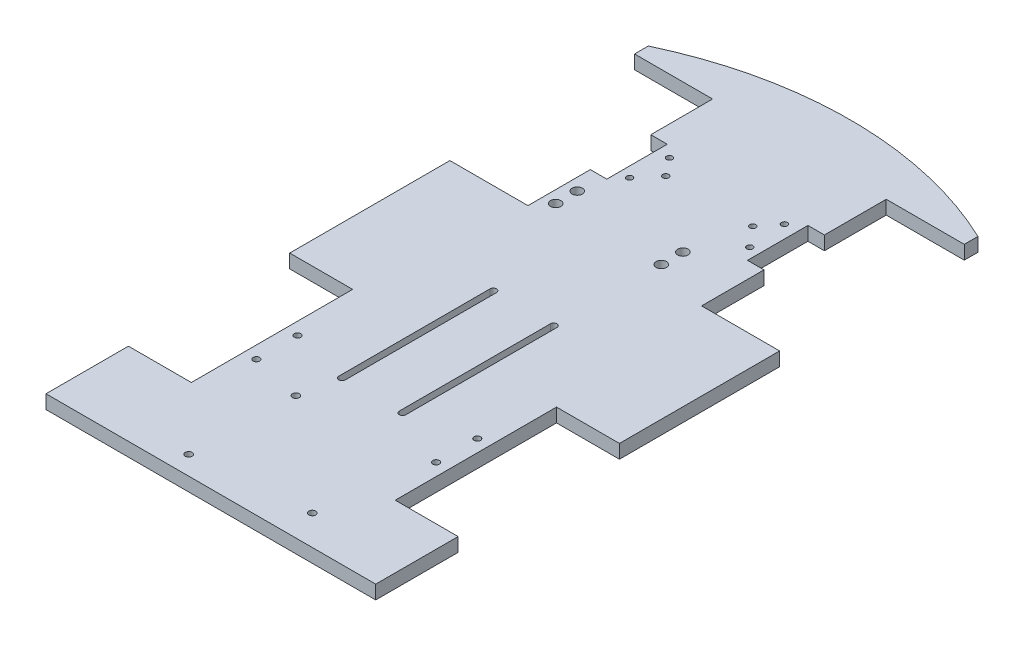
SolidWorks part; units mm, degrees
material "Oak"
ref_plane "Front Plane" through (0, 0, 0) normal (0, 0, 1) x (1, 0, 0)
ref_plane "Top Plane" through (0, 0, 0) normal (0, 1, 0) x (1, 0, 0)
ref_plane "Right Plane" through (0, 0, 0) normal (1, 0, 0) x (0, 0, -1)
sketch "Sketch1" plane through (0, 0, 0) normal (0, 1, 0) x (1, 0, 0)
  line L0 (50.292, 32.512) -> (76.2, 32.512) construction
  line L1 (0, 0) -> (0, -280.955) construction
  line L2 (0, 66.1738) -> (0, -229.362)
  line L3 (76.2, -229.362) -> (0, -229.362)
  line L7 (50.292, 32.512) -> (50.292, -32.512) construction
  line L8 (50.292, -32.512) -> (76.2, -32.512) construction
  line L9 (76.2, 32.512) -> (76.2, -32.512) construction
  line L10 (50.292, 32.512) -> (76.2, -32.512) construction
  line L11 (50.292, -32.512) -> (76.2, 32.512) construction
  line L18 (50.292, -119.888) -> (76.2, -119.888) construction
  line L19 (50.292, -119.888) -> (50.292, -184.912) construction
  line L20 (50.292, -184.912) -> (76.2, -184.912) construction
  line L21 (76.2, -119.888) -> (76.2, -184.912) construction
  line L22 (50.292, -119.888) -> (76.2, -184.912) construction
  line L23 (50.292, -184.912) -> (76.2, -119.888) construction
  line L25 (-76.2, 0) -> (76.2, 0) construction
  line L27 (-76.2, -152.4) -> (76.2, -152.4) construction
  line L28 (76.2, 0) -> (76.2, -152.4) construction
  line L33 (40.132, -42.672) -> (76.2, -42.672)
  line L34 (40.132, 42.672) -> (40.132, 14.097)
  line L35 (40.132, 42.672) -> (76.2, 42.672)
  line L36 (47.117, -191.262) -> (76.2, -191.262)
  line L37 (47.117, -116.713) -> (47.117, -191.262)
  line L38 (47.117, -116.713) -> (76.2, -116.713)
  line L43 (76.2, -42.672) -> (76.2, -116.713)
  line L45 (76.2, 42.672) -> (76.2, 49.022)
  line L47 (76.2, -191.262) -> (76.2, -229.362)
  line L55 (32.512, -13.843) -> (40.132, -13.843)
  line L56 (32.512, 14.097) -> (32.512, -13.843)
  line L57 (32.512, 14.097) -> (40.132, 14.097)
  line L58 (40.132, -13.843) -> (40.132, -42.672)
  arc A0 (0, 66.1738) -> (76.2, 49.022) centre (0, -111.6688) cw
  point P9 (63.246, 0)
  point P19 (63.246, -152.4)
  dimension "D7" = 3.175
  dimension "D8" = 6.35
  dimension "D12" = 7.62
  dimension "D16" = 6.35
  dimension "D1" = 152.4
  dimension "D2" = 152.4
  dimension "D3" = 126.492
  dimension "D4" = 25.908
  dimension "D6" = 3.175
  dimension "D9" = 10.16
  dimension "D10" = 10.16
  dimension "D5" = 65.024
  dimension "D11" = 10.16
  dimension "D13" = 27.94
  dimension "D14" = 28.575
  dimension "D15" = 38.1
extrude "Chassis" add sketch "Sketch1" along normal blind 6.35 contours L47 L36 L37 L38 L43 L33 L34 L55 L56 L57 L35 L45 region at (30.845, 0, 91.965)
mirror "Mirror1" about plane through (0, 6.35, 0) normal (1, 0, 0) of "Chassis"
sketch "Sketch2" plane through (0, 0, 0) normal (0, 1, 0) x (1, 0, 0)
  line L0 (-47.117, -116.713) -> (-47.117, -191.262) construction
  line L1 (-47.117, -191.262) -> (-76.2, -191.262) construction
  line L2 (47.117, -116.713) -> (47.117, -191.262) construction
  line L3 (47.117, -191.262) -> (76.2, -191.262) construction
  line L4 (15.367, -84.7659) -> (15.367, -154.6159)
  line L5 (12.367, -84.7659) -> (12.367, -154.6159)
  line L6 (-12.573, -84.7659) -> (-12.573, -154.6159)
  line L7 (-15.573, -84.7659) -> (-15.573, -154.6159)
  line L8 (47.117, -116.713) -> (76.2, -116.713) construction
  circle A0 centre (-26.5557, 9.17) radius 1.3716 construction
  circle A1 centre (-17.7031, -172.3599) radius 1.5875
  circle A2 centre (-17.7031, -172.3599) radius 1.5875
  circle A3 centre (-18.9731, -220.6199) radius 1.5875
  circle A4 centre (-18.9731, -220.6199) radius 1.5875
  circle A5 centre (33.0969, -215.5399) radius 1.5875
  circle A6 centre (33.0969, -215.5399) radius 1.5875
  circle A7 centre (-20.1056, 0.9994) radius 1.3716 construction
  circle A8 centre (-27.7865, -8.0406) radius 1.3716 construction
  circle A9 centre (26.5557, 9.17) radius 1.3716 construction
  circle A10 centre (20.1056, 0.9994) radius 1.3716 construction
  circle A11 centre (27.7865, -8.0406) radius 1.3716 construction
  circle A12 centre (14.2672, -25.46) radius 2.3813 construction
  circle A13 centre (14.2672, -35.4295) radius 2.3813 construction
  circle A14 centre (-34.5516, -25.46) radius 2.3813 construction
  circle A15 centre (-34.5516, -35.4295) radius 2.3813 construction
  arc A20 (15.367, -154.6159) -> (12.367, -154.6159) centre (13.867, -154.6159) cw
  arc A21 (-12.573, -154.6159) -> (-15.573, -154.6159) centre (-14.073, -154.6159) cw
  circle A24 centre (-26.5557, 9.17) radius 1.3716
  circle A25 centre (-20.1056, 0.9994) radius 1.3716
  circle A26 centre (-27.7865, -8.0406) radius 1.3716
  circle A27 centre (26.5557, 9.17) radius 1.3716
  circle A28 centre (20.1056, 0.9994) radius 1.3716
  circle A29 centre (27.7865, -8.0406) radius 1.3716
  circle A30 centre (14.2672, -25.46) radius 2.3812
  circle A31 centre (14.2672, -35.4295) radius 2.3813
  circle A32 centre (-34.5516, -25.46) radius 2.3813
  circle A33 centre (-34.5516, -35.4295) radius 2.3812
  arc A34 (15.367, -84.7659) -> (12.367, -84.7659) centre (13.867, -84.7659) ccw
  arc A35 (-12.573, -84.7659) -> (-15.573, -84.7659) centre (-14.073, -84.7659) ccw
  circle A38 centre (-41.402, -147.875) radius 1.5
  circle A39 centre (-41.402, -166.925) radius 1.5
  circle A40 centre (41.402, -147.6053) radius 1.5
  circle A41 centre (41.402, -166.6553) radius 1.5
  dimension "D4" = 3
  dimension "D5" = 3
  dimension "D10" = 19.05
  dimension "D14" = 3
  dimension "D15" = 3
  dimension "D22" = 31.9471
  dimension "D6" = 19.05
  dimension "D7" = 5.715
  dimension "D8" = 5.715
  dimension "D9" = 24.337
  dimension "D11" = 5.715
  dimension "D12" = 5.715
  dimension "D13" = 24.6067
  dimension "D16" = 31.75
  dimension "D17" = 69.85
  dimension "D18" = 69.85
  dimension "D20" = 3
  dimension "D21" = 3
  dimension "1.1" = 27.94
  dimension "D1" = 0
  dimension "D2" = 0
  dimension "D3" = 0
extrude "Cut-Extrude1" cut sketch "Sketch2" along normal blind 17.78
